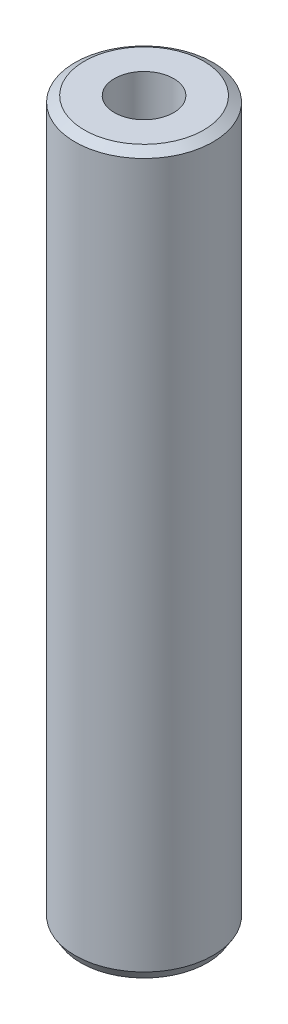
SolidWorks part; units mm, degrees
ref_plane "Front Plane" through (0, 0, 0) normal (0, 0, 1) x (1, 0, 0)
ref_plane "Top Plane" through (0, 0, 0) normal (0, 1, 0) x (1, 0, 0)
ref_plane "Right Plane" through (0, 0, 0) normal (1, 0, 0) x (0, 0, -1)
sketch "Sketch1" plane through (0, 0, 0) normal (0, 1, 0) x (1, 0, 0)
  circle A0 centre (0, 0) radius 57.5
  dimension "SHAFT_OD" = 115
extrude "Boss-Extrude1" add sketch "Sketch1" along normal blind 600
sketch "Sketch2" plane through (0, 0, 0) normal (0, 1, 0) x (1, 0, 0)
  circle A0 centre (0, 0) radius 24.6804
  dimension "BORE_D" = 49.3608
extrude "Cut-Extrude1" cut sketch "Sketch2" along normal through all
chamfer "Chamfer1" distance 4.7892 angle 58.202 2 edges at (0, 600, 57.5) (0, 0, 57.5) first distance on face at (0, 600, 57.5) first distance on face at (0, 0, 24.6804)
